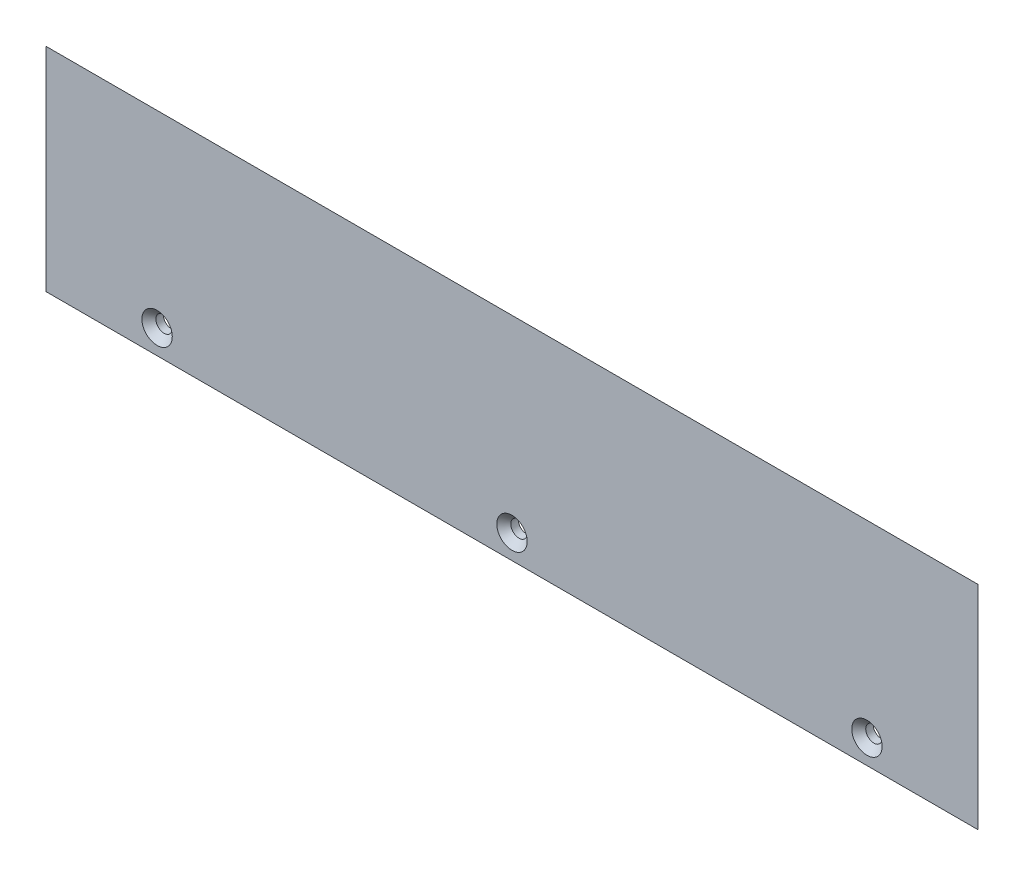
SolidWorks part; units mm, degrees
ref_plane "Front Plane" through (0, 0, 0) normal (0, 0, 1) x (1, 0, 0)
ref_plane "Top Plane" through (0, 0, 0) normal (0, 1, 0) x (1, 0, 0)
ref_plane "Right Plane" through (0, 0, 0) normal (1, 0, 0) x (0, 0, -1)
sketch "Sketch1" plane through (0, 0, 0) normal (0, 0, 1) x (1, 0, 0)
  line L1 (0, 0) -> (193, 0)
  line L2 (0, 0) -> (0, 44)
  line L3 (0, 44) -> (193, 44)
  line L4 (193, 0) -> (193, 44)
  dimension "D1" = 44
  dimension "D2" = 193
extrude "Boss-Extrude1" add sketch "Sketch1" along normal blind 3
chamfer "Chamfer1" distance 3 angle 45 3 edges at (0, 22, 0) (96.5, 44, 0) (193, 22, 0)
sketch "Sketch2" plane through (0, 0, 3) normal (0, 0, 1) x (1, 0, 0)
  line L0 (0, 5) -> (193, 5) construction
  line L1 (0, 44) -> (0, 0) construction
  line L2 (193, 0) -> (193, 44) construction
  line L3 (0, 0) -> (193, 0) construction
  point P8 (23, 5)
  point P9 (96.5, 5)
  point P10 (170, 5)
  dimension "D1" = 5
  dimension "D2" = 23
  dimension "D3" = 23
hole_wizard "CSK for M3 Flat Head Machine Screw1" positions "Sketch4" profile "Sketch3" countersink size "M3" standard "ANSI Metric" end condition through all
sketch "Sketch4" plane through (0, 0, 3) normal (0, 0, 1) x (1, 0, 0)
  point P0 (23, 5)
  point P3 (96.5, 5)
  point P6 (170, 5)
sketch "Sketch3" plane through (23, 5, 3) normal (1, 0, 0) x (0, -1, 0)
  line L0 (0, 0) -> (0, 3)
  line L1 (0, 3) -> (1.7, 3)
  line L2 (1.7, 3) -> (1.7, 1.45)
  line L3 (1.7, 1.45) -> (3.15, 0)
  line L5 (3.15, 0) -> (0, 0)
  line L6 (-1.7, 1.45) -> (-3.15, 0) construction
  line L11 (0, -6.35) -> (0, 107.95) construction
  dimension "Thru Hole Dia." = 3.4
  dimension "Thru Hole Depth" = 3
  dimension "Near C'Sink Dia." = 6.3
  dimension "Near C'Sink Angle" = 90
